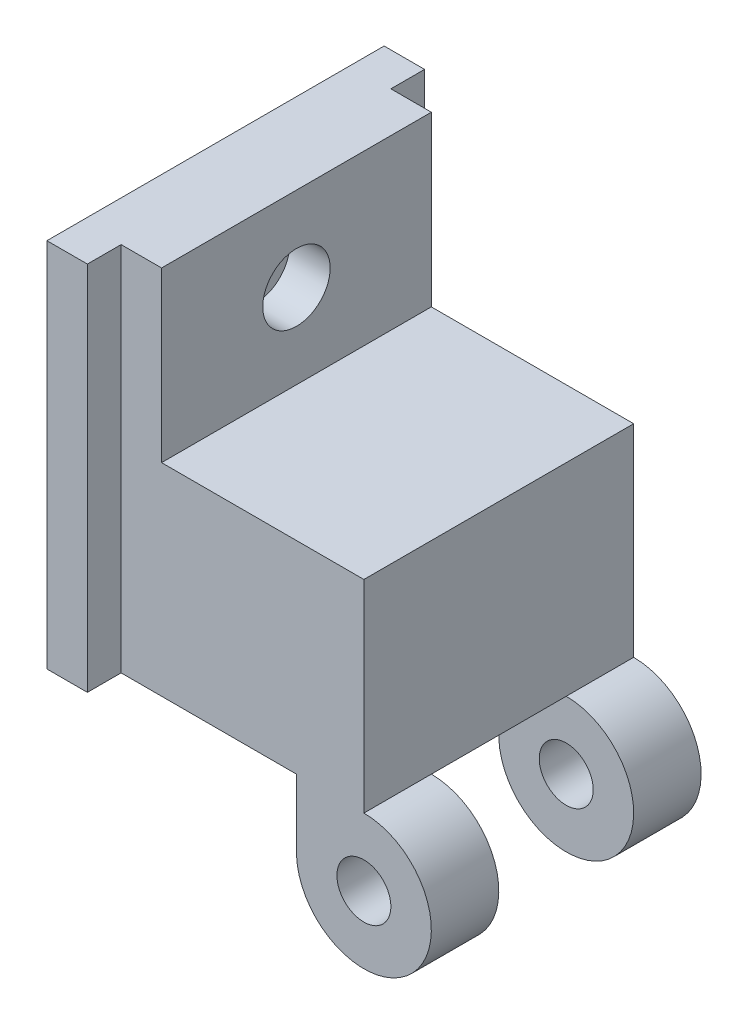
SolidWorks part; units mm, degrees
ref_plane "Front Plane" through (0, 0, 0) normal (0, 0, 1) x (1, 0, 0)
ref_plane "Top Plane" through (0, 0, 0) normal (0, 1, 0) x (1, 0, 0)
ref_plane "Right Plane" through (0, 0, 0) normal (1, 0, 0) x (0, 0, -1)
sketch "Sketch1" plane through (0, 0, 0) normal (1, 0, 0) x (0, 0, -1)
  line L1 (-10, -7.5) -> (10, -7.5)
  line L2 (-10, -7.5) -> (-10, 7.5)
  line L3 (-10, 7.5) -> (10, 7.5)
  line L4 (10, -7.5) -> (10, 7.5)
  line L5 (-10, -7.5) -> (10, 7.5) construction
  line L6 (-10, 7.5) -> (10, -7.5) construction
  point P0 (0, 0)
  dimension "D1" = 20
  dimension "D2" = 15
extrude "Boss-Extrude1" add sketch "Sketch1" along normal blind 15
sketch "Sketch2" plane through (0, 0, 10) normal (0, 0, 1) x (1, 0, 0)
  line L0 (15, -7.5) -> (10.0156, -7.5)
  line L1 (10.0156, -12.1058) -> (10.0156, -7.5)
  line L2 (15, -7.5) -> (0, -7.5) construction
  circle A0 centre (15, -12.5) radius 2
  arc A2 (10.0156, -12.1058) -> (15, -7.5) centre (15, -12.5) ccw
  arc A3 (10.0156, -12.1058) -> (15, -7.5) centre (15, -12.5) cw construction
  dimension "D1" = 4
extrude "Boss-Extrude2" add sketch "Sketch2" against normal blind 5
mirror "Mirror1" about plane through (0, 0, 0) normal (0, 0, 1) of "Boss-Extrude2"
sketch "Sketch3" plane through (0, 7.5, 0) normal (0, -1, 0) x (1, 0, 0)
  line L4 (-3, 10) -> (-3, 12.5)
  line L5 (-3, 12.5) -> (-6, 12.5)
  line L6 (-6, 12.5) -> (-6, -12.5)
  line L7 (-6, -12.5) -> (-3, -12.5)
  line L8 (-3, -12.5) -> (-3, -10)
  line L9 (-3, 10) -> (0, 10)
  line L10 (0, 10) -> (0, -10)
  line L11 (0, -10) -> (-3, -10)
  point P1 (-1.5844, 9.9304)
  point P3 (-6, 0)
  dimension "D1" = 25
  dimension "D2" = 3
  dimension "D3" = 3
extrude "Boss-Extrude3" add sketch "Sketch3" along normal up to surface (15 mm away) and the other way blind 12.5 up to face at (8.7578, -7.5, 0)
sketch "Sketch4" plane through (0, 0, 0) normal (1, 0, 0) x (0, 0, -1)
  line L0 (10, 20) -> (10, 7.5) construction
  circle A0 centre (0, 13.75) radius 1.5
  circle A1 centre (0, 13.75) radius 2.5
  point P4 (0, 0)
  point P8 (10, 13.75)
  dimension "D2" = 3
  dimension "D1" = 1
extrude "Cut-Extrude1" cut sketch "Sketch4" against normal up to surface (6 mm away) contours A0 region at (0, 13.75, 0) up to face at (-6, 6.25, 0)
extrude "Cut-Extrude2" cut sketch "Sketch4<3>" against normal blind 3
sketch "Sketch4<3>" plane through (0, 0, 0) normal (1, 0, 0) x (0, 0, -1) same geometry as "Sketch4"
